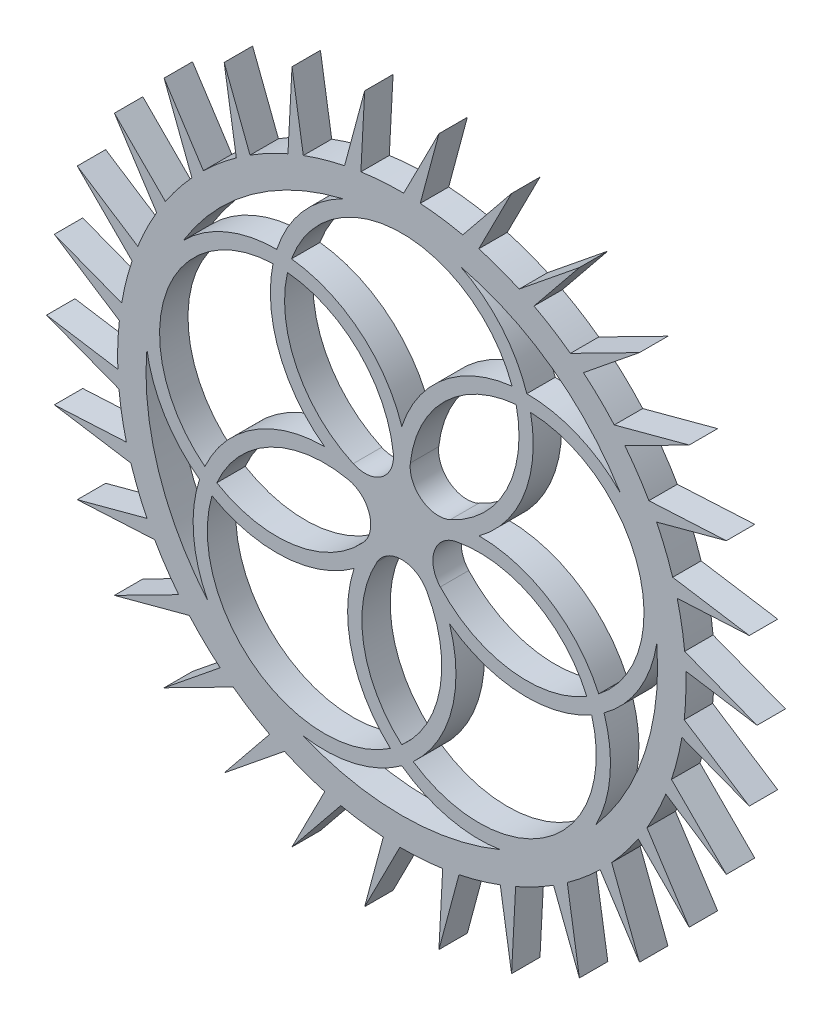
SolidWorks part; units mm, degrees
ref_plane "Front Plane" through (0, 0, 0) normal (0, 0, 1) x (1, 0, 0)
ref_plane "Top Plane" through (0, 0, 0) normal (0, 1, 0) x (1, 0, 0)
ref_plane "Right Plane" through (0, 0, 0) normal (1, 0, 0) x (0, 0, -1)
sketch "Sketch1" plane through (0, 0, 0) normal (0, 0, 1) x (1, 0, 0)
  line L0 (16.0535, 41.8207) -> (125, 0) construction
  line L1 (3.0589, 19.3133) -> (125, 0) construction
  line L2 (125, 0) -> (99.5205, 9.7806)
  line L3 (125, 0) -> (99.9211, 3.972)
  circle A0 centre (0, 0) radius 19.554 construction
  circle A1 centre (0, 0) radius 44.796 construction
  circle A2 centre (0, 0) radius 125 construction
  circle A3 centre (0, 0) radius 100
  circle A4 centre (0, 0) radius 90
  point P9 (100, 0)
  point P11 (90, 0)
  dimension "tooth front base circle" = 39.108
  dimension "tooth back base circle" = 89.592
  dimension "escapement wheel diameter" = 250
  dimension "clearance" = 25
  dimension "ring thickness" = 10
extrude "Boss-Extrude1" add sketch "Sketch1" along normal blind 10 contours A3 A4 | A3 L3 L2 region at (108.1665, 4.579, 0) region at (96.9414, 6.6847, 0)
pattern_circular "CirPattern1" count 30 over 360 about axis through (0, 0, 10) along (0, 0, -1) of "Boss-Extrude1"
sketch "Sketch2" plane through (0, 0, 0) normal (0, 0, 1) x (1, 0, 0)
  circle A0 centre (0, 46.25) radius 41.25
  circle A1 centre (0, 46.25) radius 46.25
  circle A3 centre (0, 0) radius 90 construction
  point P3 (0, 92.5)
  point P4 (0, 87.5)
  point P5 (0, 0)
  point P6 (0, 90)
  dimension "D1" = 2.5
  dimension "D2" = 5
extrude "Boss-Extrude2" add sketch "Sketch2" along normal blind 10
pattern_circular "CirPattern3" count 5 over 360 about axis through (0, 0, 10) along (0, 0, -1) of "Boss-Extrude2" reverse direction yes
fillet "Fillet1" radius 10 5 edges at (3.7573, 5.1715, 5) (-3.7573, 5.1715, 5) (-6.0794, -1.9753, 5) (0, -6.3923, 5) (6.0794, -1.9753, 5)
ref_axis "Axis1" through (0, 0, 0) along (0, 0, 1)
